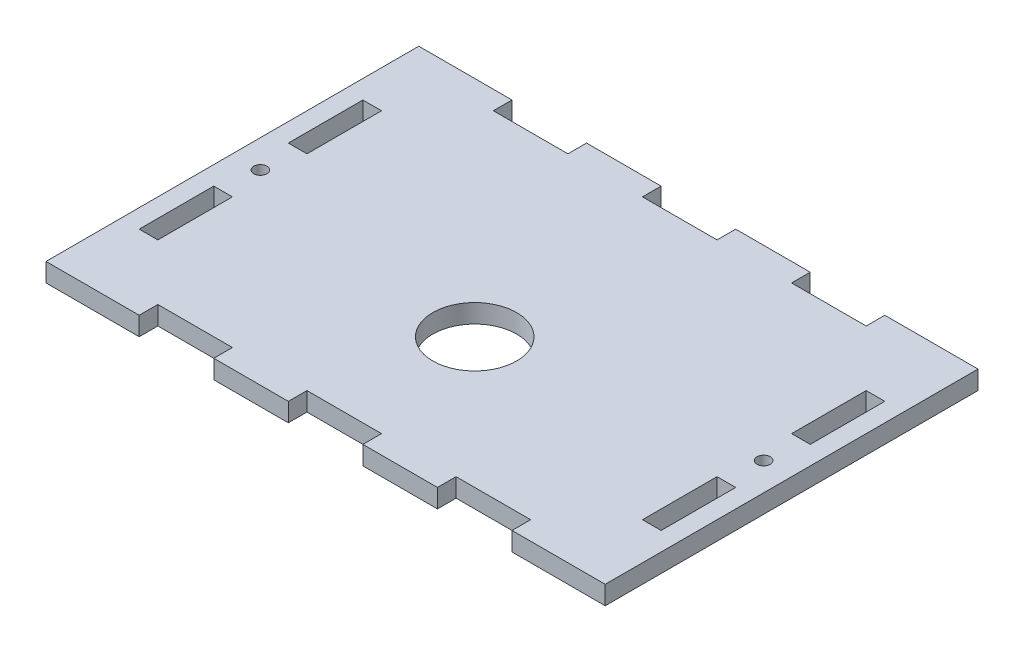
SolidWorks part; units mm, degrees
ref_plane "Front Plane" through (0, 0, 0) normal (0, 0, 1) x (1, 0, 0)
ref_plane "Top Plane" through (0, 0, 0) normal (0, 1, 0) x (1, 0, 0)
ref_plane "Right Plane" through (0, 0, 0) normal (1, 0, 0) x (0, 0, -1)
sketch "Sketch1" plane through (0, 0, 0) normal (0, 1, 0) x (1, 0, 0)
  line L1 (0, 0) -> (190.5, 0)
  line L2 (0, 0) -> (0, 127)
  line L3 (0, 127) -> (190.5, 127)
  line L4 (190.5, 0) -> (190.5, 127)
  dimension "D1" = 127
  dimension "D2" = 190.5
extrude "Boss-Extrude1" add sketch "Sketch1" along normal blind 6.35
sketch "Sketch13" plane through (0, 6.35, 0) normal (0, 1, 0) x (1, 0, 0)
  line L0 (0, 0) -> (190.5, 0) construction
  line L1 (31.75, 0) -> (57.15, 0)
  line L2 (31.75, 0) -> (31.75, 6.35)
  line L3 (31.75, 6.35) -> (57.15, 6.35)
  line L4 (57.15, 0) -> (57.15, 6.35)
  line L5 (82.55, 6.35) -> (107.95, 6.35)
  line L6 (107.95, 0) -> (107.95, 6.35)
  line L7 (82.55, 0) -> (107.95, 0)
  line L8 (82.55, 0) -> (82.55, 6.35)
  line L9 (133.35, 6.35) -> (158.75, 6.35)
  line L10 (158.75, 0) -> (158.75, 6.35)
  line L11 (133.35, 0) -> (158.75, 0)
  line L12 (133.35, 0) -> (133.35, 6.35)
  line L17 (31.75, 6.35) -> (82.55, 6.35) construction
  line L18 (0, 127) -> (0, 0) construction
  dimension "D1" = 25.4
  dimension "D2" = 6.35
  dimension "D4" = 50.8
  dimension "D5" = 31.75
  dimension "D3" = 3
extrude "Cut-Extrude6" cut sketch "Sketch13" against normal blind 6.35
pattern_linear "LPattern7" count 2 spacing 120.65 along (0, 0, -1) of "Cut-Extrude6"
sketch "Sketch14" plane through (0, 6.35, 0) normal (0, 1, 0) x (1, 0, 0)
  line L0 (0, 127) -> (0, 0) construction
  line L1 (6.35, 25.4) -> (12.7, 25.4)
  line L2 (6.35, 25.4) -> (6.35, 50.8)
  line L3 (6.35, 50.8) -> (12.7, 50.8)
  line L4 (12.7, 25.4) -> (12.7, 50.8)
  line L5 (0, 0) -> (31.75, 0) construction
  line L6 (177.8, 50.8) -> (184.15, 50.8)
  line L7 (177.8, 25.4) -> (177.8, 50.8)
  line L8 (184.15, 25.4) -> (184.15, 50.8)
  line L9 (177.8, 25.4) -> (184.15, 25.4)
  line L10 (177.8, 101.6) -> (184.15, 101.6)
  line L11 (177.8, 76.2) -> (177.8, 101.6)
  line L12 (184.15, 76.2) -> (184.15, 101.6)
  line L13 (177.8, 76.2) -> (184.15, 76.2)
  line L14 (6.35, 101.6) -> (12.7, 101.6)
  line L15 (6.35, 76.2) -> (6.35, 101.6)
  line L16 (12.7, 76.2) -> (12.7, 101.6)
  line L17 (6.35, 76.2) -> (12.7, 76.2)
  dimension "D1" = 25.4
  dimension "D2" = 6.35
  dimension "D3" = 6.35
  dimension "D4" = 25.4
  dimension "D5" = 2
  dimension "D6" = 2
extrude "Cut-Extrude7" cut sketch "Sketch14" against normal blind 6.35
hole_wizard "#8 Clearance Hole1" positions "Sketch16" profile "Sketch15" hole size "#8" standard "ANSI Inch"
sketch "Sketch16" plane through (0, 6.35, 0) normal (0, 1, 0) x (1, 0, 0)
  line L0 (12.7, 50.8) -> (6.35, 50.8) construction
  line L1 (6.35, 50.8) -> (6.35, 25.4) construction
  line L2 (184.15, 50.8) -> (177.8, 50.8) construction
  line L3 (177.8, 50.8) -> (177.8, 25.4) construction
  point P0 (9.525, 63.5)
  point P3 (9.525, 50.8)
  point P8 (180.975, 63.5)
  dimension "D1" = 12.7
  dimension "D2" = 3.175
  dimension "D3" = 12.7
  dimension "D4" = 3.175
sketch "Sketch15" plane through (9.525, 6.35, -63.5) normal (1, 0, 0) x (0, 0, 1)
  line L0 (0, 0) -> (0, 11.5107)
  line L1 (0, 11.5107) -> (2.2479, 10.16)
  line L2 (2.2479, 10.16) -> (2.2479, 0)
  line L5 (2.2479, 0) -> (0, 0)
  line L10 (0, 11.5107) -> (-2.2479, 10.16) construction
  line L11 (0, -6.35) -> (0, 107.95) construction
  dimension "Hole Dia." = 4.4958
  dimension "Hole Depth" = 10.16
  dimension "Drill Angle" = 118
sketch "Sketch18" plane through (0, 6.35, 0) normal (0, 1, 0) x (1, 0, 0)
  line L0 (0, 127) -> (0, 0) construction
  line L1 (107.95, 6.35) -> (82.55, 6.35) construction
  circle A0 centre (95.25, 50.8) radius 14.2875
  dimension "D1" = 28.575
  dimension "D2" = 95.25
  dimension "D3" = 44.45
extrude "Cut-Extrude9" cut sketch "Sketch18" against normal blind 7.62
equation "\"THICK\"= .25"
